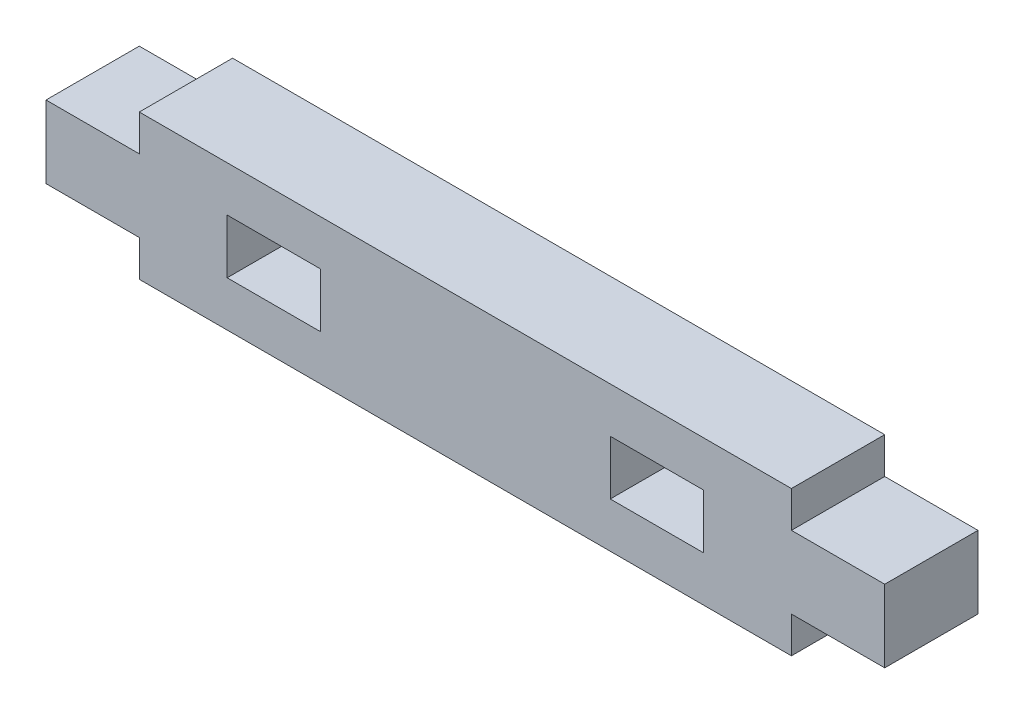
SolidWorks part; units mm, degrees
ref_plane "Front Plane" through (0, 0, 0) normal (0, 0, 1) x (1, 0, 0)
ref_plane "Top Plane" through (0, 0, 0) normal (0, 1, 0) x (1, 0, 0)
ref_plane "Right Plane" through (0, 0, 0) normal (1, 0, 0) x (0, 0, -1)
sketch "Sketch1" plane through (0, 0, 0) normal (0, 0, 1) x (1, 0, 0)
  line L0 (0, 19.9873) -> (0, -14.0711) construction
  line L1 (0, -18.7321) -> (0, 18.7321) construction
  line L2 (-18, 0) -> (0, 0)
  line L3 (-18, 8) -> (18, 8)
  line L4 (18, 8) -> (18, 6)
  line L5 (18, 6) -> (23.15, 6)
  line L6 (23.15, 6) -> (23.15, 2)
  line L7 (23.15, 2) -> (18, 2)
  line L8 (18, 2) -> (18, 0)
  line L9 (25.465, 0) -> (-25.465, 0) construction
  line L10 (18, 0) -> (0, 0)
  line L18 (-18, 2) -> (-18, 0)
  line L19 (-23.15, 2) -> (-18, 2)
  line L20 (-23.15, 6) -> (-23.15, 2)
  line L21 (-18, 6) -> (-23.15, 6)
  line L22 (-18, 8) -> (-18, 6)
  point P33 (0, 8)
  dimension "D1" = 5.15
  dimension "D2" = 4
  dimension "D3" = 8
  dimension "D4" = 18
extrude "Boss-Extrude1" add sketch "Sketch1" along normal blind 5.15
sketch "Sketch2" plane through (0, 0, 5.15) normal (0, 0, 1) x (1, 0, 0)
  line L0 (23.15, 4) -> (0, 4) construction
  line L1 (23.15, 2) -> (23.15, 6) construction
  line L2 (0, -2.8325) -> (0, 2.8325) construction
  line L3 (0, 18.7739) -> (0, -12.3131) construction
  line L4 (8, 5.5) -> (13.15, 5.5)
  line L5 (8, 5.5) -> (8, 2.5)
  line L6 (8, 2.5) -> (13.15, 2.5)
  line L7 (13.15, 5.5) -> (13.15, 2.5)
  line L8 (-13.15, 5.5) -> (-13.15, 2.5)
  line L9 (-8, 2.5) -> (-13.15, 2.5)
  line L10 (-8, 5.5) -> (-8, 2.5)
  line L11 (-8, 5.5) -> (-13.15, 5.5)
  point P10 (8, 4)
  dimension "D1" = 8
  dimension "D2" = 5.15
  dimension "D3" = 3
extrude "Cut-Extrude1" cut sketch "Sketch2" against normal through all
